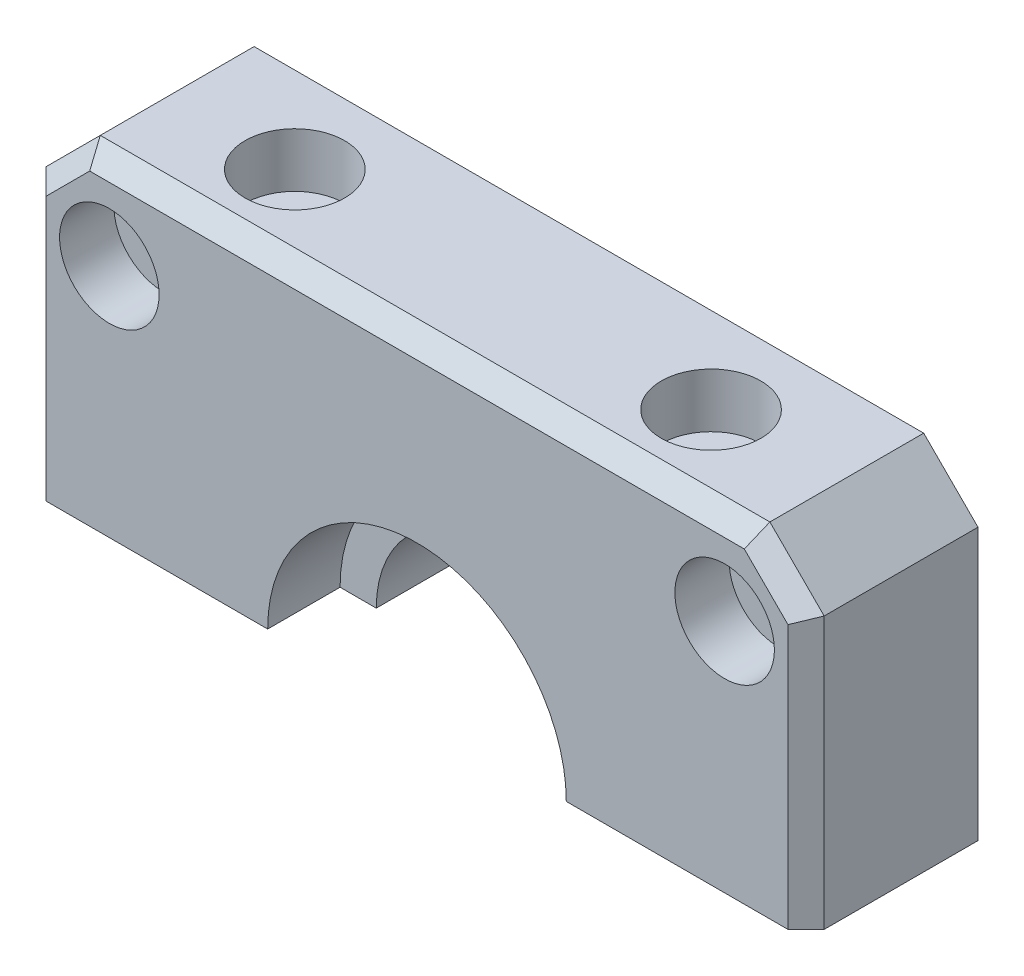
SolidWorks part; units mm, degrees
ref_plane "前基準面" through (0, 0, 0) normal (0, 0, 1) x (1, 0, 0)
ref_plane "上基準面" through (0, 0, 0) normal (0, 1, 0) x (1, 0, 0)
ref_plane "右基準面" through (0, 0, 0) normal (1, 0, 0) x (0, 0, -1)
sketch "草圖1" plane through (0, 0, 0) normal (0, 0, 1) x (1, 0, 0)
  line L0 (0, 0) -> (0, 40) construction
  line L1 (-20.5, 40) -> (20.5, 40)
  line L2 (20.5, 40) -> (20.5, 30)
  line L3 (-20.5, 40) -> (-20.5, 30)
  line L4 (44.891, -2.2465) -> (36.2308, 2.7535)
  line L5 (44.891, -2.2465) -> (24.391, -37.7535)
  line L6 (24.391, -37.7535) -> (15.7308, -32.7535)
  line L7 (-24.391, -37.7535) -> (-15.7308, -32.7535)
  line L8 (-24.391, -37.7535) -> (-44.891, -2.2465)
  line L9 (-44.891, -2.2465) -> (-36.2308, 2.7535)
  line L10 (-36.2308, 2.7535) -> (-20.5, 30)
  line L11 (20.5, 30) -> (36.2308, 2.7535)
  line L12 (15.7308, -32.7535) -> (-15.7308, -32.7535)
  line L13 (0, 0) -> (34.641, -20) construction
  line L14 (0, 0) -> (-34.641, -20) construction
  circle A0 centre (0, 0) radius 18
  point P6 (0, 0)
  point P9 (0, 40)
  point P22 (0, 0)
  point P23 (0, 0)
  dimension "D1" = 36
  dimension "D2" = 40
  dimension "D3" = 20.5
  dimension "D4" = 10
  dimension "D6" = 20.5
  dimension "D7" = 3
  dimension "D8" = 40
  dimension "D9" = 40
  dimension "D10" = 72.7535
  dimension "D5" = 3
extrude "填料-伸長1" add sketch "草圖1" along normal blind 20
sketch "草圖2" plane through (-20.5, 0, 0) normal (-1, 0, 0) x (0, 0, 1)
  line L0 (20, 35) -> (0, 35) construction
  line L1 (20, 40) -> (20, 30) construction
  line L2 (0, 40) -> (0, 30) construction
  circle A0 centre (15, 35) radius 2.75
  dimension "D1" = 5.5
  dimension "D2" = 5
extrude "除料-伸長1" cut sketch "草圖2" against normal through all
pattern_circular "環狀複製排列1" count 3 over 360 about axis through (0, 0, 20) along (0, 0, 1) of "除料-伸長1"
sketch "草圖3" plane through (-20.5, 0, 0) normal (-1, 0, 0) x (0, 0, 1)
  line L0 (0, 40) -> (2.6795, 30) construction
  line L3 (20, 30) -> (0, 30) construction
  line L4 (0, 40) -> (0, 30) construction
  dimension "D1" = 15
sketch "草圖4" plane through (0, 0, 0) normal (0, 0, -1) x (-1, 0, 0)
  point P0 (-20.5, 40)
ref_plane "平面1" through (0, 2.6795, 10) normal (0, 0.2588, 0.9659) x (1, 0, 0)
sketch "草圖5" plane through (0, 2.6795, 10) normal (0, 0.2588, 0.9659) x (1, 0, 0)
  line L0 (0, 38.637) -> (0, 0) construction
  line L1 (20.5, 38.637) -> (-20.5, 38.637) construction
  line L2 (-14.5, 33.637) -> (14.5, 33.637) construction
  line L3 (-14.5, 33.637) -> (-14.5, 38.637)
  line L4 (-15, 38.637) -> (15, 38.637)
  line L5 (-15, 38.637) -> (-15, 18.637)
  line L6 (-15, 18.637) -> (15, 18.637)
  line L7 (15, 38.637) -> (15, 18.637)
  line L8 (14.5, 33.637) -> (14.5, 38.637)
  arc A0 (-9.4338, 22.6255) -> (9.4338, 22.6255) centre (0, 33.637) ccw
  arc A1 (-11.0115, 24.2032) -> (-9.4338, 22.6255) centre (-12, 21.637) ccw
  arc A2 (11.0115, 24.2032) -> (9.4338, 22.6255) centre (12, 21.637) cw
  arc A3 (11.0115, 24.2032) -> (14.5, 33.637) centre (0, 33.637) ccw
  arc A4 (-14.5, 33.637) -> (-11.0115, 24.2032) centre (0, 33.637) ccw
  arc A5 (13.6107, 38.637) -> (-13.6107, 38.637) centre (0, 33.637) ccw
  point P17 (0, 18.637)
  dimension "D1" = 29
  dimension "D3" = 5.5
  dimension "D2" = 5
  dimension "D4" = 12
  dimension "D5" = 12
  dimension "D6" = 30
  dimension "D7" = 20
  dimension "D8" = 0.5
  dimension "D9" = 0.5
  dimension "D10" = 0.8893
  dimension "D11" = 0.8893
  dimension "D12" = 14.5
  dimension "D13" = 14.5
extrude "除料-伸長2" cut sketch "草圖5" along normal blind 9 and the other way through all contours A2 A3 L4 A1 A0 region at (0, 31.0405, 2.4007)
sketch "草圖6" plane through (0, 2.6795, 10) normal (0, 0.2588, 0.9659) x (1, 0, 0)
  line L0 (0, 0) -> (0, 38.637) construction
  line L2 (-15, 38.637) -> (15, 38.637)
  line L3 (-15, 38.637) -> (-15, 18.637)
  line L4 (-15, 18.637) -> (15, 18.637)
  line L5 (15, 38.637) -> (15, 18.637)
extrude "除料-伸長3" cut sketch "草圖6" against normal through all and the other way blind 5
sketch "草圖7" plane through (0, 3.9736, 14.8296) normal (0, -0.2588, -0.9659) x (-1, 0, 0)
  circle A0 centre (12, 21.637) radius 2.75
  circle A1 centre (-12, 21.637) radius 2.75
extrude "除料-伸長4" cut sketch "草圖7" against normal blind 5
pattern_circular "環狀複製排列2" count 3 over 360 about axis through (0, 0, 0) along (0, 0, 1) of "除料-伸長2", "除料-伸長3", "除料-伸長4"
fillet "圓角1" radius 3 6 edges at (-43.516, -4.628, 0) (-25.766, -35.372, 0) (25.766, -35.372, 0) (43.516, -4.628, 0) (17.75, 40, 0) (-17.75, 40, 0)
sketch "草圖11" plane through (0, 0, 20) normal (0, 0, 1) x (1, 0, 0)
  line L0 (0, 40) -> (0, -32.7535) construction
  line L1 (20.5, 40) -> (-20.5, 40) construction
  line L2 (-15.7308, -32.7535) -> (15.7308, -32.7535) construction
  line L3 (-14.5, 18) -> (-21.5, 18)
  line L4 (-14.5, -18) -> (-21.5, -18)
  line L5 (-21.5, 18) -> (-21.5, -18)
  line L6 (14.5, 18) -> (14.5, 10.563)
  line L7 (-14.5, 18) -> (-14.5, 10.563)
  line L8 (0, 0) -> (-21.5, 0) construction
  line L9 (21.5, 18) -> (21.5, -18)
  line L10 (14.5, -18) -> (21.5, -18)
  line L11 (14.5, 18) -> (21.5, 18)
  line L12 (-14.5, -10.563) -> (-14.5, -18)
  line L13 (14.5, -10.563) -> (14.5, -18)
  circle A0 centre (0, 0) radius 14.5 construction
  circle A1 centre (0, 0) radius 17.9395
  circle M20 centre (0, 0) radius 18
  dimension "D1" = 29
  dimension "D2" = 7
  dimension "D3" = 14.5
  dimension "D4" = 18
extrude "填料-伸長2" add sketch "草圖11" along normal blind 20 contours L12 L7 L3 L5 L4 M20 | L13 L10 L9 L11 L6 M20 region at (-18.5275, 0, 20) region at (18.5275, 0, 20)
sketch "草圖12" plane through (0, 0, 40) normal (0, 0, 1) x (1, 0, 0)
  line L0 (-14.5, 18) -> (-21.5, 18) construction
  line L1 (21.5, -18) -> (-21.5, -18)
  line L2 (21.5, -18) -> (21.5, 18)
  line L3 (21.5, 18) -> (-21.5, 18)
  line L4 (-21.5, -18) -> (-21.5, 18)
  circle A0 centre (0, 0) radius 8
  dimension "D1" = 16
extrude "填料-伸長3" add sketch "草圖12" along normal blind 9
chamfer "導角1" distance 1.5 angle 60 1 edges at (0, 18, 40) first distance on face at (0, 18, 32.25)
sketch "草圖13" plane through (0, 18, 0) normal (0, 1, 0) x (1, 0, 0)
  line L0 (0, -49) -> (0, 0) construction
  line L1 (15, -46) -> (-15, -46)
  line L2 (15, -46) -> (15, -16)
  line L3 (15, -16) -> (-15, -16)
  line L4 (-15, -46) -> (-15, -16)
  line L5 (21.5, -49) -> (-21.5, -49) construction
  line L6 (15, -31) -> (-15, -31) construction
  circle A0 centre (0, -31) radius 14.5
  circle A1 centre (12, -43) radius 1.5
  circle A2 centre (-12, -43) radius 1.5
  point P9 (0, -46)
  dimension "D3" = 29
  dimension "D7" = 3
  dimension "D1" = 30
  dimension "D2" = 30
  dimension "D4" = 12
  dimension "D5" = 12
  dimension "D6" = 18
extrude "除料-伸長7" cut sketch "草圖13" against normal blind 20 contours A2 | A1 region at (-12, 18, 43)
sketch "草圖15" plane through (0, 18, 0) normal (0, 1, 0) x (1, 0, 0)
  line L0 (15, -16) -> (-15, -16) construction
  line L1 (14.5, -40) -> (-14.5, -40)
  line L2 (14.5, -40) -> (14.5, -16)
  line L3 (14.5, -16) -> (-14.5, -16)
  line L4 (-14.5, -40) -> (-14.5, -16)
  line L5 (-14.5, -41.5) -> (-14.5, -20) construction
  line L6 (14.5, -41.5) -> (14.5, -20) construction
  line L7 (-14.5, -40) -> (14.5, -40) construction
extrude "除料-伸長9" cut sketch "草圖15" against normal blind 80
fillet "圓角2" radius 2.5 3 edges at (-34.641, -20, 20) (34.641, -20, 20) (0, 40, 20)
fillet "圓角3" radius 1 30 edges at (-20.5, 33.75, 20) (-20.5, 39.2678, 19.2678) (-20.5, 33.5, 0) (-20.5, 39.1213, 0.8787) (-39.4784, 0.8785, 20) (-44.2569, -1.8804, 19.2678) (-39.2619, 1.0035, 0) (-44.1301, -1.8071, 0.8787) (-18.9784, -34.6285, 20) (-23.7569, -37.3874, 19.2678) (-18.7619, -34.5035, 0) (-23.6301, -37.3142, 0.8787) (18.9784, -34.6285, 20) (23.7569, -37.3874, 19.2678) (18.7619, -34.5035, 0) (23.6301, -37.3142, 0.8787) (39.4784, 0.8785, 20) (44.2569, -1.8804, 19.2678) (39.2619, 1.0035, 0) (44.1301, -1.8071, 0.8787) (20.5, 33.75, 20) (20.5, 39.2678, 19.2678) (20.5, 33.5, 0) (20.5, 39.1213, 0.8787) (-20.5, 40, 10.25) (-44.891, -2.2465, 10.25) (-24.391, -37.7535, 10.25) (24.391, -37.7535, 10.25) (44.891, -2.2465, 10.25) (20.5, 40, 10.25)
sketch "草圖17" plane through (0, 18, 0) normal (0, 1, 0) x (1, 0, 0)
  line L0 (0, 0) -> (0, -49) construction
  line L1 (15, -31) -> (-15, -31) construction
  line L2 (14.5, -21.5528) -> (11, -21.5528)
  line L3 (14.5, -41.5) -> (14.5, -20) construction
  line L4 (8.8318, -16) -> (8.8318, -19.5)
  line L5 (15, -16) -> (-15, -16) construction
  line L6 (14.5, -21.5528) -> (14.5, -16)
  line L7 (14.5, -16) -> (8.8318, -16)
  line L8 (-14.5, -16) -> (-8.8318, -16)
  line L9 (-14.5, -21.5528) -> (-14.5, -16)
  line L10 (-8.8318, -16) -> (-8.8318, -19.5)
  line L11 (-14.5, -21.5528) -> (-11, -21.5528)
  circle A0 centre (12, -19) radius 1.5
  arc A1 (11, -21.5528) -> (8.8318, -19.5) centre (0, -31) ccw
  arc A2 (-11, -21.5528) -> (-8.8318, -19.5) centre (0, -31) cw
  circle A3 centre (-12, -19) radius 1.5
  dimension "D3" = 3
  dimension "D4" = 29
  dimension "D1" = 12
  dimension "D2" = 12
  dimension "D5" = 3.5
  dimension "D6" = 3.5
extrude "填料-伸長4" add sketch "草圖17" against normal blind 5
sketch "草圖18" plane through (0, 0, 16) normal (0, 0, -1) x (-1, 0, 0)
  circle A0 centre (0, 0) radius 18
extrude "除料-伸長11" cut sketch "草圖18" against normal up to surface (5.5528 mm away) up to face at (-12.75, 15.5, 21.5528)
sketch "草圖14" plane through (0, 18, 0) normal (0, 1, 0) x (1, 0, 0)
  line L1 (-15, -46) -> (-15, -16) construction
  line L2 (15, -16) -> (-15, -16)
  line L3 (15, -16) -> (15, -21.5528)
  line L4 (15, -21.5528) -> (-15, -21.5528)
  line L7 (-15, -16) -> (-15, -21.5528)
  line L8 (11, -21.5528) -> (14.5, -21.5528) construction
extrude "除料-伸長14" cut sketch "草圖14" along normal blind 13
chamfer "導角3" distance 3 angle 46 1 edges at (0, 31, 20) first distance on face at (0, -0.1461, 20)
ref_plane "平面2" through (0, -15.1166, 26.1827) normal (0, -0.5, 0.866) x (-1, 0, 0)
sketch "草圖19" plane through (0, -15.1166, 26.1827) normal (0, -0.5, 0.866) x (-1, 0, 0)
  line L0 (0, 0) -> (0, 28.3654) construction
  line L1 (17.7308, 28.3654) -> (-17.7308, 28.3654) construction
  circle A0 centre (0, 19.7998) radius 2.5
  dimension "D1" = 5
extrude "除料-伸長15" cut sketch "草圖19" against normal through all both and the other way through all
sketch "草圖20" plane through (0, -15.1166, 26.1827) normal (0, -0.5, 0.866) x (-1, 0, 0)
  circle A0 centre (0, 19.7998) radius 2.75
  dimension "D1" = 5.5
extrude "除料-伸長16" cut sketch "草圖20" against normal blind 12
fillet "圓角4" radius 3 2 edges at (8.5956, -32.7535, 16) (-8.5956, -32.7535, 16)
fillet "圓角5" radius 1 5 edges at (0, -32.7535, 0) (28.3654, 16.3768, 20) (28.3654, 16.3768, 0) (-28.3654, 16.3768, 20) (-28.3654, 16.3768, 0)
chamfer "導角4" distance 3 angle 45 4 edges at (21.5, -18, 34.5) (-21.5, -18, 34.5) (-21.5, 18, 34.5) (21.5, 18, 34.5)
fillet "圓角6" radius 1 6 edges at (14.5, -31.8748, 15.1213) (-14.5, -31.8748, 15.1213) (14.5, -25.3768, 20) (14.5, -20.2094, 16) (-14.5, -20.2094, 16) (-14.5, -25.3768, 20)
chamfer "導角5" distance 2.5 angle 45 12 edges at (14.7929, -18, 19.7071) (16.75, 18, 20) (20, 16.5, 20) (21.5, 0, 20) (20, -16.5, 20) (17, -18, 20) (-14.7929, -18, 19.7071) (-16.75, 18, 20) (-20, 16.5, 20) (-17, -18, 20) (-20, -16.5, 20) (-21.5, 0, 20)
sketch "草圖21" plane through (-20.5, 0, 0) normal (-1, 0, 0) x (0, 0, 1)
  circle A0 centre (15, 35) radius 2.75
extrude "填料-伸長5" add sketch "草圖21" against normal blind 31 from offset 5 offset against normal yes
pattern_circular "環狀複製排列3" count 3 over 360 about axis through (0, 0, 0) along (0, 0, 1) of "填料-伸長5"
sketch "草圖22" plane through (0, 0, 49) normal (0, 0, 1) x (1, 0, 0)
  line L0 (-21.5, 15) -> (-18.5, 18)
  line L1 (-18.5, 18) -> (18.5, 18)
  line L2 (18.5, 18) -> (21.5, 15)
  line L3 (21.5, 15) -> (21.5, 0)
  line L4 (21.5, -15) -> (21.5, 15) construction
  line L5 (21.5, 0) -> (6.25, 0)
  line L6 (-21.5, 15) -> (-21.5, -15) construction
  line L7 (-21.5, 0) -> (-21.5, 15)
  line L8 (-6.25, 0) -> (-21.5, 0)
  arc A0 (6.25, 0) -> (-6.25, 0) centre (0, 0) ccw
  dimension "D1" = 12.5
extrude "填料-伸長6" add sketch "草圖22" along normal blind 9.5
sketch "草圖16" plane through (0, 0, 49) normal (0, 0, 1) x (1, 0, 0)
  line L0 (0, -18) -> (0, 18) construction
  line L1 (-18.5, -18) -> (18.5, -18) construction
  line L2 (21.5, 18) -> (-21.5, 18) construction
  line L3 (21.5, 0) -> (-21.5, 0) construction
  line L5 (-21.5, 18) -> (-21.5, -18) construction
  circle A0 centre (17, -13) radius 1.5
  circle A1 centre (-17, -13) radius 1.5
  circle A2 centre (-17, 13) radius 1.5
  circle A3 centre (17, 13) radius 1.5
  dimension "D1" = 3
  dimension "D2" = 17
  dimension "D3" = 13
extrude "除料-伸長10" cut sketch "草圖16" along normal through all
sketch "草圖23" plane through (0, -18, 0) normal (0, -1, 0) x (1, 0, 0)
  line L1 (-49.4886, 49) -> (52.9623, 49)
  line L2 (-49.4886, 49) -> (-49.4886, -10.055)
  line L3 (-49.4886, -10.055) -> (52.9623, -10.055)
  line L4 (52.9623, 49) -> (52.9623, -10.055)
extrude "除料-伸長17" cut sketch "草圖23" against normal through all both and the other way through all
sketch "草圖24" plane through (0, 0, 0) normal (0, -1, 0) x (1, 0, 0)
  line L0 (0, 58.5) -> (0, 49) construction
  line L1 (6.25, 58.5) -> (-6.25, 58.5) construction
  line L2 (-6.25, 49) -> (6.25, 49) construction
  line L3 (-21.5, 53.75) -> (0, 53.75) construction
  line L4 (-21.5, 58.5) -> (-21.5, 49) construction
  circle A0 centre (-11.5, 53.75) radius 1.5
  circle A1 centre (11.5, 53.75) radius 1.5
  dimension "D1" = 3
  dimension "D2" = 10
sketch "草圖25" plane through (0, 0, 58.5) normal (0, 0, 1) x (1, 0, 0)
  circle A0 centre (0, 0) radius 8.25
  dimension "D1" = 16.5
extrude "除料-伸長18" cut sketch "草圖25" against normal blind 4
extrude "除料-伸長19" cut sketch "草圖24" against normal through all
sketch "草圖26" plane through (0, 0, 58.5) normal (0, 0, 1) x (1, 0, 0)
  circle A0 centre (-17, 13) radius 2.75
  circle A1 centre (17, 13) radius 2.75
  dimension "D1" = 5.5
  dimension "D2" = 5.5
extrude "除料-伸長20" cut sketch "草圖26" against normal blind 3
sketch "草圖27" plane through (0, 18, 0) normal (0, 1, 0) x (1, 0, 0)
  circle A0 centre (11.5, -53.75) radius 2.75
  circle A1 centre (-11.5, -53.75) radius 2.75
  dimension "D1" = 5.5
  dimension "D2" = 5.5
extrude "除料-伸長21" cut sketch "草圖27" against normal blind 3
chamfer "導角6" distance 1 angle 45 5 edges at (21.5, 7.5, 58.5) (20, 16.5, 58.5) (-21.5, 7.5, 58.5) (-20, 16.5, 58.5) (0, 18, 58.5)
